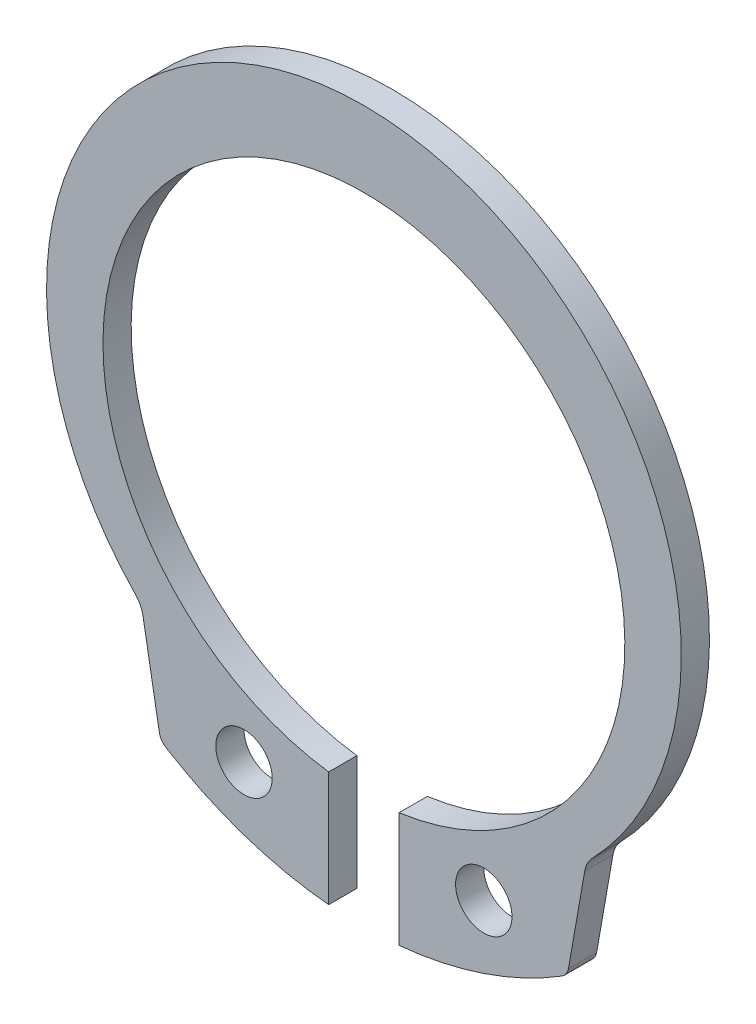
SolidWorks part; units mm, degrees
ref_plane "前视" through (0, 0, 0) normal (0, 0, 1) x (1, 0, 0)
ref_plane "上视" through (0, 0, 0) normal (0, 1, 0) x (1, 0, 0)
ref_plane "右视" through (0, 0, 0) normal (1, 0, 0) x (0, 0, -1)
sketch "尺寸草图" plane through (0, 0, 0) normal (0, 0, 1) x (1, 0, 0)
  line L0 (0, 7.25) -> (0, -11.25) construction
  circle A0 centre (0, 0) radius 11.25
  point P5 (0, 2.05)
  point P6 (0, -7.65)
  point P7 (0, -9.15)
  point P8 (0, -8.15)
  point P9 (0, 0.05)
  point P10 (0, 15.55)
  point P11 (0, 16.55)
  point P12 (0, -4.42)
  point P13 (0, 4.08)
  point P14 (0, 6.58)
  dimension "DD" = 22.5
  dimension "d" = 18.5
  dimension "c" = 0.67
  dimension "RR" = 13.3
  dimension "r1" = 11.2
  dimension "r2" = 1
  dimension "d1" = 2
  dimension "b1" = 2.5
  dimension "b2" = 8.5
  dimension "L" = 14.5
  dimension "r3" = 0.5
  dimension "s" = 1
sketch "草图1" plane through (0, 0, 0) normal (0, 0, 1) x (1, 0, 0)
  line L0 (0, 0) -> (0, -22.3757) construction
  line L1 (-1.25, -9.8352) -> (-1.25, -13.9111)
  line L2 (-7.8312, -8.3317) -> (-7.25, -11.6277)
  line L3 (-7.8854, -8.0239) -> (-7.8854, -11.8451) construction
  line L4 (1.25, -9.8352) -> (1.25, -13.9111)
  line L5 (7.8312, -8.3317) -> (7.25, -11.6277)
  line L6 (0, 7.25) -> (0, -11.25) construction
  arc A0 (8.0963, -7.811) -> (-8.0963, -7.811) centre (0, 0) ccw
  arc A1 (1.25, -9.8352) -> (-1.25, -9.8352) centre (0, -0.67) ccw
  arc A2 (-1.25, -13.9111) -> (-7.0216, -11.9655) centre (0, -0.67) cw
  arc A3 (-7.0216, -11.9655) -> (-7.25, -11.6277) centre (-6.7576, -11.5408) cw
  circle A4 centre (-4.25, -11.0323) radius 1
  arc A5 (1.25, -13.9111) -> (7.0216, -11.9655) centre (0, -0.67) ccw
  circle A6 centre (4.25, -11.0323) radius 1
  arc A7 (7.0216, -11.9655) -> (7.25, -11.6277) centre (6.7576, -11.5408) ccw
  arc A8 (-7.8312, -8.3317) -> (-8.0963, -7.811) centre (-8.816, -8.5054) ccw
  arc A9 (7.8312, -8.3317) -> (8.0963, -7.811) centre (8.816, -8.5054) cw
  point P13 (-7.2117, -11.8451)
  point P29 (7.8854, -8.0239)
  dimension "D2" = 22.5
  dimension "D3" = 18.5
  dimension "D4" = 13.3
  dimension "D7" = 0.5
  dimension "D9" = 2
  dimension "D12" = 1
  dimension "D1" = 0.67
  dimension "D5" = 2.5
  dimension "D6" = 10
  dimension "D8" = 14.5
  dimension "D10" = 11.2
  dimension "D11" = 8.5
extrude "基体-拉伸" add sketch "草图1" along normal blind 0.5 and the other way blind 0.5
equation "\"D2@草图1\" = \"DD@尺寸草图\""
equation "\"D3@草图1\" = \"d@尺寸草图\""
equation "\"D1@草图1\" = \"c@尺寸草图\""
equation "\"D4@草图1\" = \"RR@尺寸草图\""
equation "\"D7@草图1\" = \"r3@尺寸草图\""
equation "\"D10@草图1\" = \"r1@尺寸草图\""
equation "\"D5@草图1\" = \"b1@尺寸草图\""
equation "\"D11@草图1\" = \"b2@尺寸草图\""
equation "\"D8@草图1\" = \"L@尺寸草图\""
equation "\"D12@草图1\" = \"r2@尺寸草图\""
equation "\"D9@草图1\" = \"d1@尺寸草图\""
equation "\"D1@基体-拉伸\" = \"s@尺寸草图\"/2"
equation "\"D2@基体-拉伸\" = \"s@尺寸草图\"/2"
